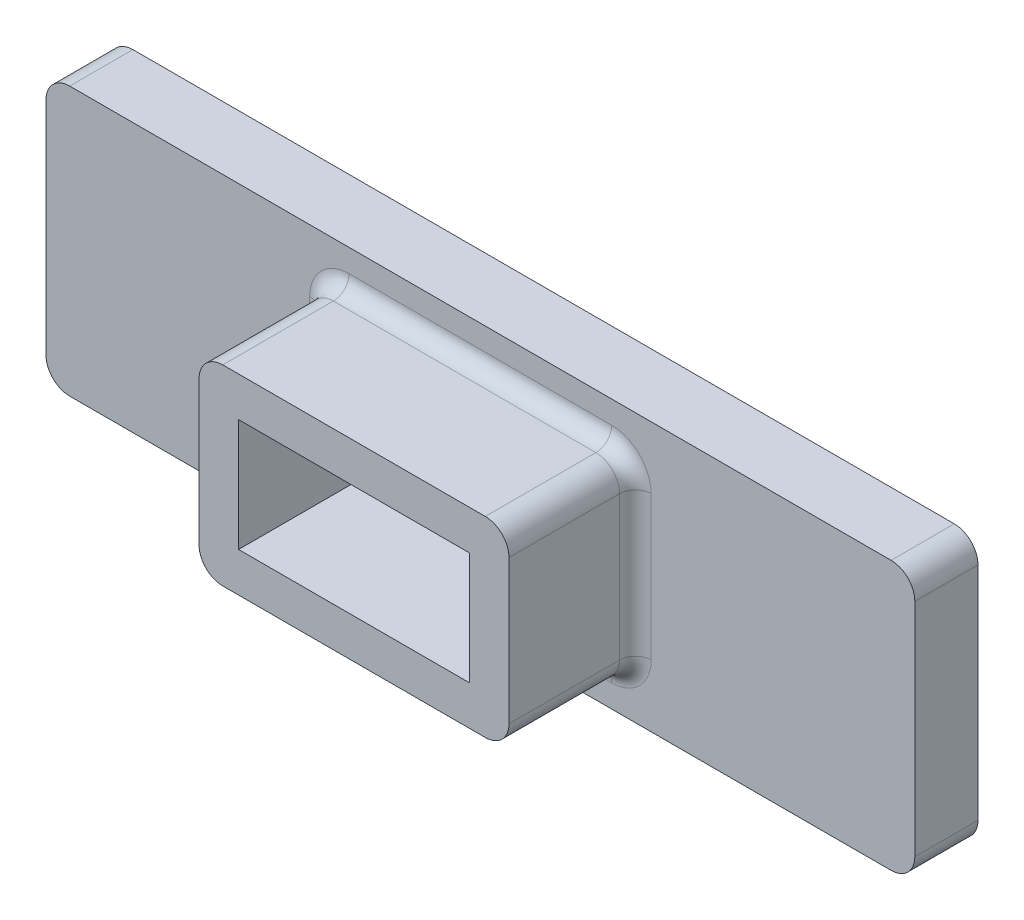
SolidWorks part; units mm, degrees
material "PLA2"
ref_plane "Front Plane" through (0, 0, 0) normal (0, 0, 1) x (1, 0, 0)
ref_plane "Top Plane" through (0, 0, 0) normal (0, 1, 0) x (1, 0, 0)
ref_plane "Right Plane" through (0, 0, 0) normal (1, 0, 0) x (0, 0, -1)
sketch "Sketch1" plane through (0, 0, 0) normal (0, 0, 1) x (1, 0, 0)
  line L1 (-34.925, 10.795) -> (34.925, 10.795)
  line L2 (-34.925, 10.795) -> (-34.925, -10.795)
  line L3 (-34.925, -10.795) -> (34.925, -10.795)
  line L4 (34.925, 10.795) -> (34.925, -10.795)
  line L5 (-34.925, 10.795) -> (34.925, -10.795) construction
  line L6 (-34.925, -10.795) -> (34.925, 10.795) construction
  point P0 (0, 0)
  dimension "D1" = 69.85
  dimension "D2" = 21.59
extrude "Boss-Extrude1" add sketch "Sketch1" along normal blind 5.08
sketch "Sketch2" plane through (0, 0, 5.08) normal (0, 0, 1) x (1, 0, 0)
  line L1 (-12.4587, 7.6962) -> (12.4587, 7.6962)
  line L2 (-12.4587, 7.6962) -> (-12.4587, -7.6962)
  line L3 (-12.4587, -7.6962) -> (12.4587, -7.6962)
  line L4 (12.4587, 7.6962) -> (12.4587, -7.6962)
  line L5 (-12.4587, 7.6962) -> (12.4587, -7.6962) construction
  line L6 (-12.4587, -7.6962) -> (12.4587, 7.6962) construction
  line L7 (-9.2837, 4.5212) -> (9.2837, 4.5212)
  line L8 (-9.2837, 4.5212) -> (-9.2837, -4.5212)
  line L9 (-9.2837, -4.5212) -> (9.2837, -4.5212)
  line L10 (9.2837, 4.5212) -> (9.2837, -4.5212)
  line L11 (-9.2837, 4.5212) -> (9.2837, -4.5212) construction
  line L12 (-9.2837, -4.5212) -> (9.2837, 4.5212) construction
  line L13 (-9.2075, 4.445) -> (9.2075, 4.445) construction
  line L14 (-9.2075, 4.445) -> (-9.2075, -4.445) construction
  line L15 (-9.2075, -4.445) -> (9.2075, -4.445) construction
  line L16 (9.2075, 4.445) -> (9.2075, -4.445) construction
  line L17 (-9.2075, 4.445) -> (9.2075, -4.445) construction
  line L18 (-9.2075, -4.445) -> (9.2075, 4.445) construction
  point P0 (0, 0)
  point P6 (0, 0)
  point P11 (0, 0)
  dimension "D1" = 3.175
  dimension "D2" = 3.175
  dimension "D3" = 8.89
  dimension "D4" = 18.415
  dimension "D5" = 0.0762
  dimension "D6" = 0.0762
extrude "Boss-Extrude2" add sketch "Sketch2" along normal blind 10.16
fillet "Fillet2" radius 1.905 8 edges at (-12.4587, 7.6962, 10.16) (12.4587, 7.6962, 10.16) (12.4587, -7.6962, 10.16) (-12.4587, -7.6962, 10.16) (34.925, 10.795, 2.54) (34.925, -10.795, 2.54) (-34.925, 10.795, 2.54) (-34.925, -10.795, 2.54)
fillet "Fillet3" radius 1.27 8 edges at (-11.9007, -7.1382, 5.08) (-12.4587, 0, 5.08) (-11.9007, 7.1382, 5.08) (0, 7.6962, 5.08) (11.9007, 7.1382, 5.08) (12.4587, 0, 5.08) (11.9007, -7.1382, 5.08) (0, -7.6962, 5.08)
